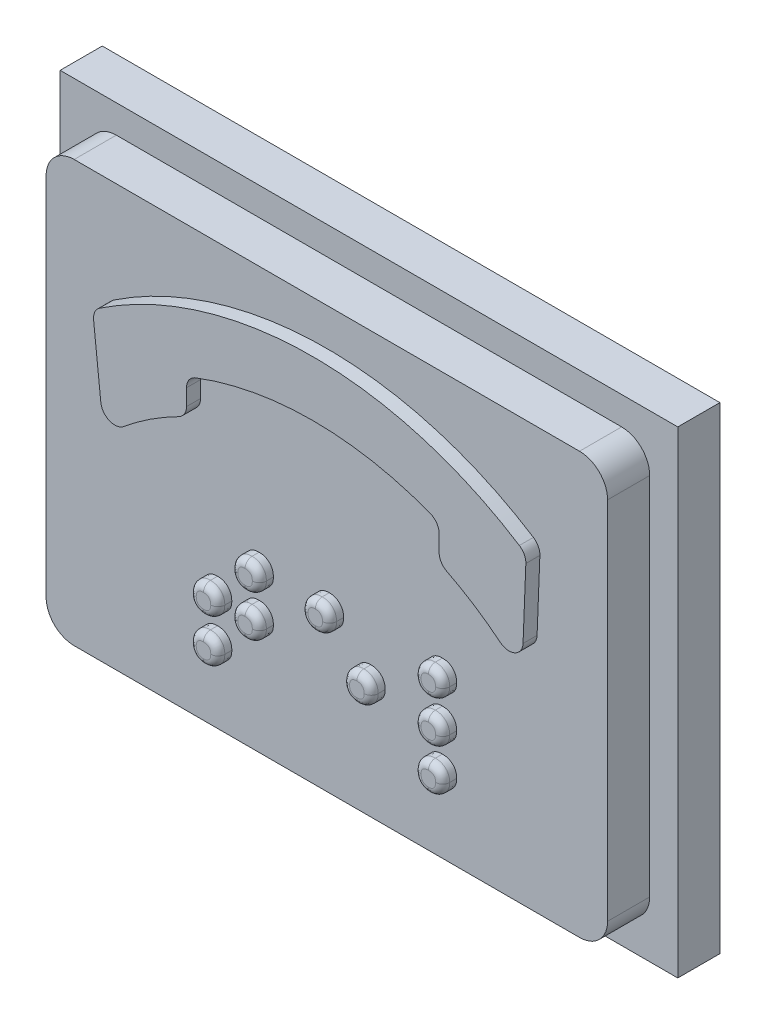
SolidWorks part; units mm, degrees
ref_plane "Front Plane" through (0, 0, 0) normal (0, 0, 1) x (1, 0, 0)
ref_plane "Top Plane" through (0, 0, 0) normal (0, 1, 0) x (1, 0, 0)
ref_plane "Right Plane" through (0, 0, 0) normal (1, 0, 0) x (0, 0, -1)
sketch "Sketch2" plane through (0, 0, 0) normal (0, 0, 1) x (1, 0, 0)
  line L1 (-22, -17) -> (22, -17)
  line L2 (-22, -17) -> (-22, 17)
  line L3 (-22, 17) -> (22, 17)
  line L4 (22, -17) -> (22, 17)
  line L5 (-22, -17) -> (22, 17) construction
  line L6 (-22, 17) -> (22, -17) construction
  point P0 (0, 0)
extrude "Boss-Extrude1" add sketch "Sketch2" along normal blind 3
sketch "Sketch3" plane through (0, 0, 0) normal (0, 0, 1) x (1, 0, 0)
  line L1 (-20, -15) -> (20, -15)
  line L2 (-20, -15) -> (-20, 15)
  line L3 (-20, 15) -> (20, 15)
  line L4 (20, -15) -> (20, 15)
  line L5 (-20, -15) -> (20, 15) construction
  line L6 (-20, 15) -> (20, -15) construction
  point P0 (0, 0)
extrude "Boss-Extrude2" add sketch "Sketch3" along normal blind 3 from surface starting at face at (0, 0, 3)
fillet "Fillet1" radius 2 4 edges at (20, 15, 4.5) (20, -15, 4.5) (-20, -15, 4.5) (-20, 15, 4.5)
sketch "Sketch4" plane through (0, 0, 0) normal (0, 0, 1) x (1, 0, 0)
  line L0 (-18, -15) -> (18, -15) construction
  line L5 (-15.6811, 7.3949) -> (-14.8931, 0)
  line L6 (15.1979, 7.7256) -> (14.8931, 0)
  line L7 (9, 4.126) -> (9, 6.5936)
  line L8 (-9, 4.126) -> (-9, 6.5936)
  arc A0 (15.1979, 7.7256) -> (-15.6811, 7.3949) centre (0, -15) ccw
  arc A1 (9, 6.5936) -> (-9, 6.5936) centre (0, -15) ccw
  arc A2 (14.8931, 0) -> (9, 4.126) centre (0, -15) ccw
  arc A3 (-9, 4.126) -> (-14.8931, 0) centre (0, -15) ccw
  text T0 "tel" font "Braille Normal" height 5
extrude "Boss-Extrude3" add sketch "Sketch4" along normal blind 1 from surface starting at face at (0, 0, 6)
fillet "Fillet3" radius 1 8 edges at (9, 6.5936, 6.5) (-9, 6.5936, 6.5) (15.1979, 7.7256, 6.5) (14.8931, 0, 6.5) (9, 4.126, 6.5) (-15.6811, 7.3949, 6.5) (-9, 4.126, 6.5) (-14.8931, 0, 6.5)
fillet "Fillet5" radius 0.5 36 edges
